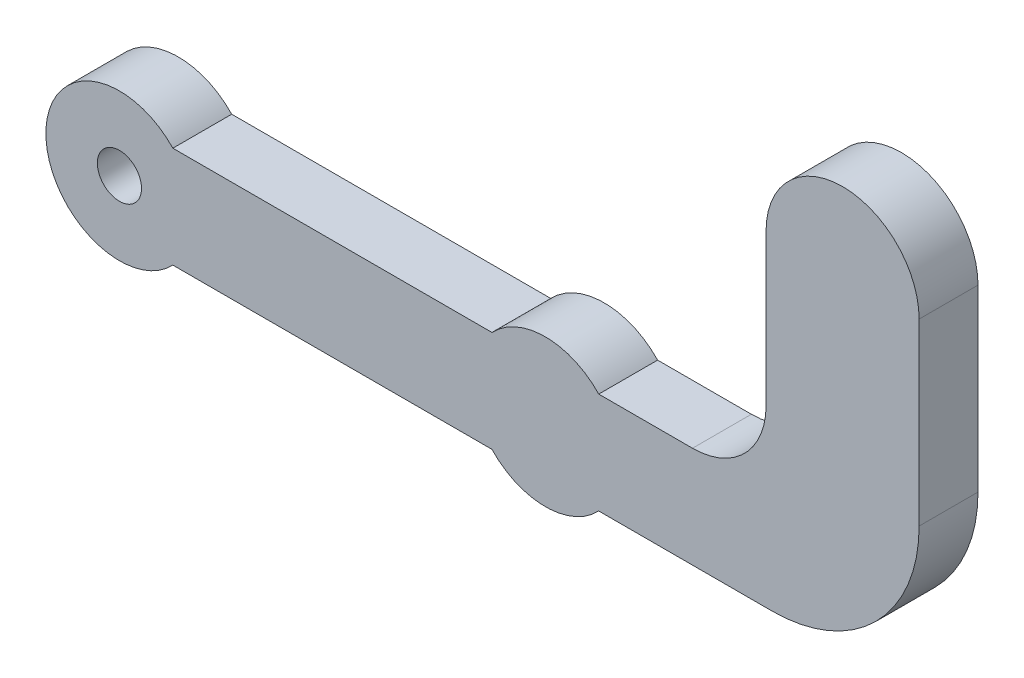
SolidWorks part; units mm, degrees
ref_plane "Alzado" through (0, 0, 0) normal (0, 0, 1) x (1, 0, 0)
ref_plane "Planta" through (0, 0, 0) normal (0, 1, 0) x (1, 0, 0)
ref_plane "Vista lateral" through (0, 0, 0) normal (1, 0, 0) x (0, 0, -1)
sketch "Croquis1" plane through (0, 0, 0) normal (0, 0, 1) x (1, 0, 0)
  line L8 (39.9959, -13.9601) -> (33.6245, -13.9601)
  line L10 (4.6845, -20.8401) -> (26.3674, -20.8401)
  line L12 (4.6845, -20.8401) -> (26.3674, -20.8401) construction
  line L13 (26.3674, -13.9601) -> (4.6845, -13.9601) construction
  line L15 (33.6245, -20.8401) -> (45.3959, -20.8401)
  line L16 (26.3674, -13.9601) -> (4.6845, -13.9601)
  line L17 (44.9959, -8.9601) -> (44.9959, 1.3399)
  line L18 (44.9959, 19.6999) -> (44.9959, -8.9601) construction
  line L19 (55.3959, -10.8401) -> (55.3959, 1.3399)
  line L20 (55.3959, -10.8401) -> (55.3959, 1.3399) construction
  arc A0 (33.6245, -13.9601) -> (26.3674, -13.9601) centre (29.9959, -17.4001) ccw
  arc A1 (4.6845, -13.9601) -> (4.6845, -20.8401) centre (1.0559, -17.4001) ccw
  circle A2 centre (50.3959, -9.1401) radius 1.5
  circle A3 centre (50.3959, 1.3399) radius 1.5
  circle A5 centre (29.9959, -17.4001) radius 1.5
  circle A6 centre (1.0559, -17.4001) radius 1.5
  arc A7 (26.3674, -20.8401) -> (33.6245, -20.8401) centre (29.9959, -17.4001) ccw
  arc A9 (44.9959, -8.9601) -> (39.9959, -13.9601) centre (39.9959, -8.9601) cw
  circle A12 centre (29.9959, -17.4001) radius 5 construction
  circle A13 centre (1.0559, -17.4001) radius 5 construction
  arc A14 (45.3959, -20.8401) -> (55.3959, -10.8401) centre (45.3959, -10.8401) ccw
  arc A16 (44.9959, 1.3399) -> (55.3959, 1.3399) centre (50.1959, 1.3399) cw
  point P2 (55.3959, 1.3399)
  point P21 (0, 0)
  dimension "D1" = 3
  dimension "D2" = 5
  dimension "D3" = 10
extrude "Saliente-Extruir1" add sketch "Croquis1" along normal blind 4
sketch "Croquis2" plane through (0, 0, 4) normal (0, 0, 1) x (1, 0, 0)
  circle A0 centre (50.3959, 1.3399) radius 1.5
  circle A1 centre (50.3959, -9.1401) radius 1.5
  circle A2 centre (29.9959, -17.4001) radius 1.5
  dimension "D1" = 3
extrude "Saliente-Extruir2" add sketch "Croquis2" against normal blind 1
